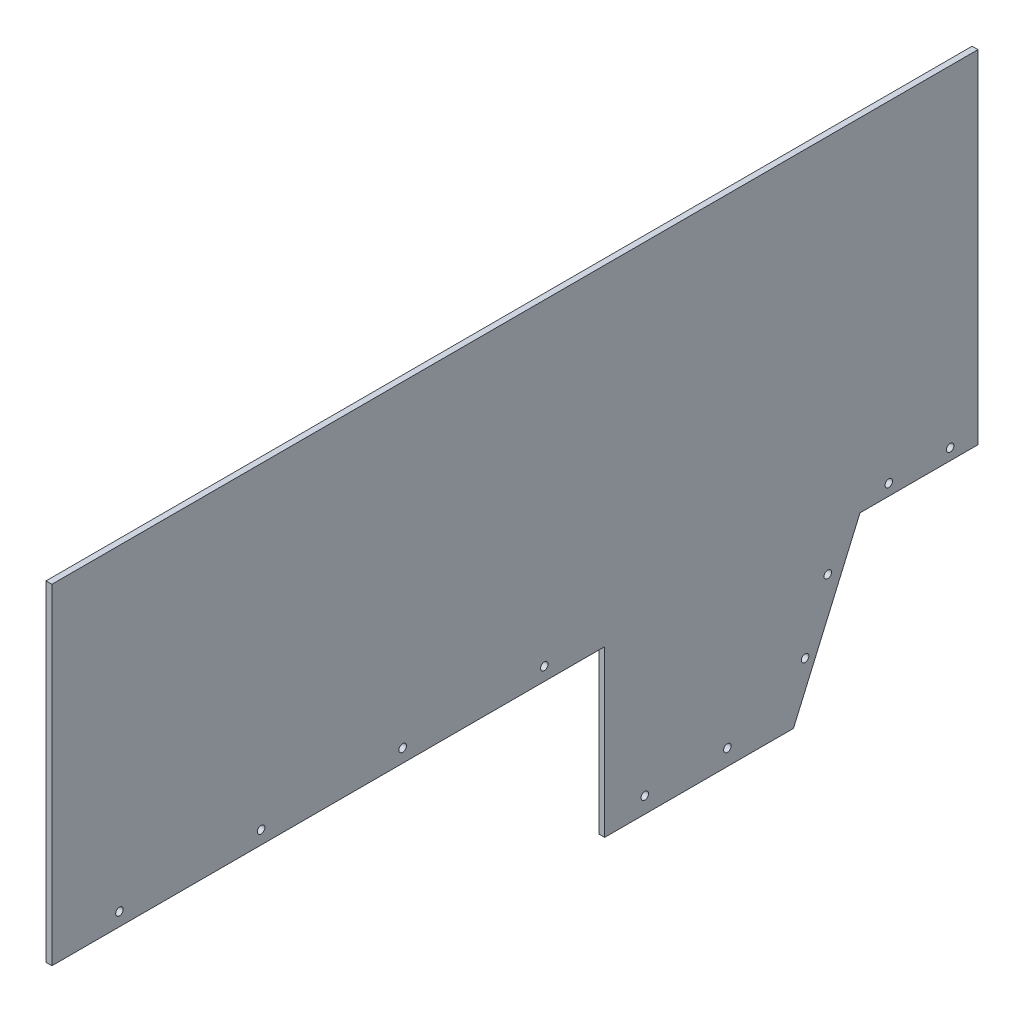
SolidWorks part; units mm, degrees
material "6061-T6 (SS)"
ref_plane "X-Y Datum" through (0, 0, 0) normal (0, 0, 1) x (1, 0, 0)
ref_plane "X-Z Datum" through (0, 0, 0) normal (0, 1, 0) x (1, 0, 0)
ref_plane "Y-Z Datum" through (0, 0, 0) normal (1, 0, 0) x (0, 0, -1)
sketch "Sketch1" plane through (0, 0, 0) normal (1, 0, 0) x (0, 0, -1)
  line L1 (-249.174, 88.9) -> (249.174, 88.9)
  line L2 (-249.174, 88.9) -> (-249.174, -88.9)
  line L3 (-249.174, -88.9) -> (249.174, -88.9)
  line L4 (249.174, 88.9) -> (249.174, -88.9)
  line L5 (-249.174, 88.9) -> (249.174, -88.9) construction
  line L6 (-249.174, -88.9) -> (249.174, 88.9) construction
  point P0 (0, 0)
  dimension "D1" = 177.8
  dimension "D2" = 498.348
extrude "Boss-Extrude1" add sketch "Sketch1" along normal mid plane 3.175
sketch "Sketch2" plane through (1.5875, 0, 0) normal (1, 0, 0) x (0, 0, -1)
  line L0 (249.174, -88.9) -> (249.174, -95.25)
  line L1 (249.174, -95.25) -> (185.674, -95.25)
  line L2 (185.674, -95.25) -> (149.8854, -177.8)
  line L3 (149.8854, -177.8) -> (48.2854, -177.8)
  line L4 (48.2854, -177.8) -> (48.2854, -88.9)
  line L5 (-249.174, -88.9) -> (249.174, -88.9) construction
  line L6 (48.2854, -88.9) -> (249.174, -88.9)
  line L8 (48.2854, -76.2) -> (48.2854, 88.9)
  line L10 (249.174, -88.9) -> (249.174, 88.9) construction
  line M10 (-249.174, -88.9) -> (249.174, -88.9)
  dimension "D1" = 6.35
  dimension "D2" = 63.5
  dimension "D3" = 88.9
  dimension "D4" = 101.6
extrude "Boss-Extrude2" add sketch "Sketch2" against normal blind 3.175 contours L4 L3 L2 L1 L0 M10 region at (1.5875, -129.6106, -113.0883)
sketch "Sketch3" plane through (1.5875, 0, 0) normal (1, 0, 0) x (0, 0, -1)
  line L0 (48.2854, -81.7704) -> (48.2854, -88.9)
  line L2 (48.2854, -81.7704) -> (15.7854, -81.7704)
  circle A1 centre (15.7854, -81.7704) radius 2.025
extrude "Cut-Extrude1" cut sketch "Sketch3" against normal through all contours A1 region at (1.5875, -81.7704, -13.8177)
pattern_linear "LPattern1" count 4 spacing 76.2 along (0, 0, 1) of "Cut-Extrude1"
sketch "Sketch4" plane through (-1.5875, 0, 0) normal (-1, 0, 0) x (0, 0, 1)
  line L0 (-69.8754, -177.8) -> (-69.8754, -169.164)
  line L2 (-149.8854, -177.8) -> (-48.2854, -177.8) construction
  line L3 (-48.2854, -169.164) -> (-69.8754, -169.164)
  line L4 (-48.2854, -177.8) -> (-48.2854, -88.9) construction
  circle A0 centre (-69.8754, -169.164) radius 2.025
extrude "Cut-Extrude2" cut sketch "Sketch4" against normal through all contours L3 A0 L0 | L0 A0 L3 region at (-1.5875, -168.8775, -70.1619) region at (-1.5875, -170.0234, -69.016)
pattern_linear "LPattern2" count 2 spacing 44.45 along (0, 0, -1) of "Cut-Extrude2"
sketch "Sketch5" plane through (-1.5875, 0, 0) normal (-1, 0, 0) x (0, 0, 1)
  line L0 (-161.6752, -150.6055) -> (-156.1289, -148.201)
  line L1 (-185.674, -95.25) -> (-149.8854, -177.8) construction
  circle A0 centre (-156.1289, -148.201) radius 2.025
extrude "Cut-Extrude3" cut sketch "Sketch5" against normal through all contours A0 region at (-1.5875, -150.1277, -155.7292)
sketch "Sketch8" plane through (-1.5875, 0, 0) normal (-1, 0, 0) x (0, 0, 1)
  line L1 (-168.3452, -115.2289) -> (-169.3867, -115.6531)
  line L2 (-156.1289, -148.201) -> (-169.3867, -115.6531)
  circle A0 centre (-168.3452, -115.2289) radius 2.025
extrude "Cut-Extrude5" cut sketch "Sketch8" against normal through all contours A0 region at (-1.5875, -116.7535, -167.1012)
sketch "Sketch9" plane through (-1.5875, 0, 0) normal (-1, 0, 0) x (0, 0, 1)
  line L0 (-201.1707, -95.25) -> (-201.1707, -89.154)
  line L1 (-249.174, -95.25) -> (-185.674, -95.25) construction
  circle A0 centre (-201.1707, -89.154) radius 2.025
extrude "Cut-Extrude6" cut sketch "Sketch9" against normal through all contours A0 region at (-1.5875, -90.5454, -199.7793)
pattern_linear "LPattern4" count 2 spacing 33.02 along (0, 0, -1) of "Cut-Extrude6"
